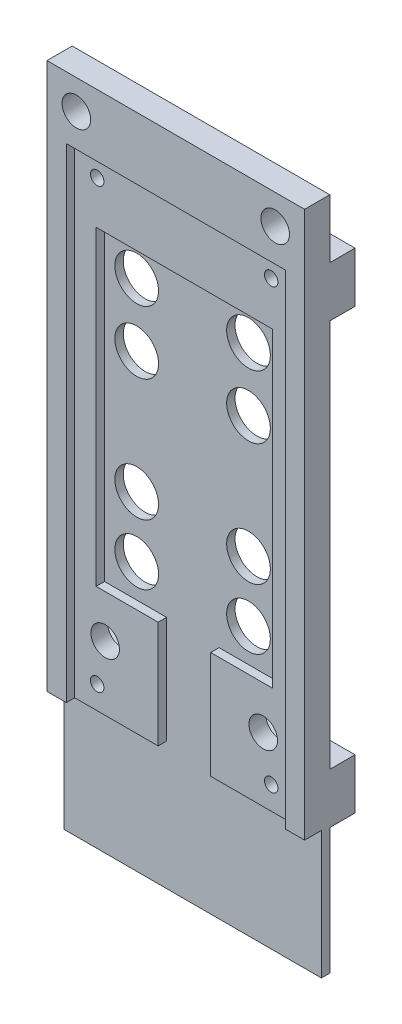
SolidWorks part; units mm, degrees
ref_plane "Front Plane" through (0, 0, 0) normal (0, 0, 1) x (1, 0, 0)
ref_plane "Top Plane" through (0, 0, 0) normal (0, 1, 0) x (1, 0, 0)
ref_plane "Right Plane" through (0, 0, 0) normal (1, 0, 0) x (0, 0, -1)
sketch "Sketch1" plane through (0, 0, 0) normal (0, 0, 1) x (1, 0, 0)
  line L0 (0, 0) -> (0, 81.2)
  line L1 (0, 81.2) -> (32.65, 81.2)
  line L2 (32.65, 81.2) -> (32.65, 0)
  line L3 (32.65, 0) -> (0, 0)
extrude "Boss-Extrude1" add sketch "Sketch1" along normal blind 1
sketch "Sketch2" plane through (0, 0, 1) normal (0, 0, 1) x (1, 0, 0)
  line L0 (0, 0) -> (0, 81.2)
  line L1 (0, 81.2) -> (32.65, 81.2)
  line L2 (32.65, 81.2) -> (32.65, 0)
  line L3 (32.65, 0) -> (31.65, 0)
  line L4 (0, 0) -> (32.65, 0) construction
  line L5 (31.65, 0) -> (31.65, 80.2)
  line L6 (0, 0) -> (1, 0)
  line L7 (1, 0) -> (1, 80.2)
  line L8 (1, 80.2) -> (31.65, 80.2)
extrude "Boss-Extrude2" add sketch "Sketch2" along normal blind 4
sketch "Sketch3" plane through (0, 0, 1) normal (0, 0, 1) x (1, 0, 0)
  line L0 (1, 80.2) -> (6.2, 80.2)
  line L1 (1, 80.2) -> (31.65, 80.2) construction
  line L2 (6.2, 80.2) -> (6.2, 75)
  line L3 (1, 80.2) -> (1, 75)
  line L4 (1, 0) -> (1, 80.2) construction
  line L5 (1, 75) -> (6.2, 75)
  line L6 (31.65, 80.2) -> (31.65, 75)
  line L7 (31.65, 80.2) -> (31.65, 0) construction
  line L8 (31.65, 75) -> (26.45, 75)
  line L9 (26.45, 75) -> (26.45, 80.2)
  line L10 (26.45, 80.2) -> (31.65, 80.2)
  line L11 (16.325, 0) -> (16.325, 15.2)
  line L12 (1, 0) -> (31.65, 0) construction
  line L13 (1, 15.2) -> (6.2, 15.2)
  line L14 (1, 15.2) -> (1, 20.4)
  line L15 (1, 20.4) -> (6.2, 20.4)
  line L16 (6.2, 20.4) -> (6.2, 15.2)
  line L17 (31.65, 15.2) -> (31.65, 20.4)
  line L18 (31.65, 15.2) -> (26.45, 15.2)
  line L19 (26.45, 15.2) -> (26.45, 20.4)
  line L20 (26.45, 20.4) -> (31.65, 20.4)
  line M18 (31.65, 0) -> (31.65, 80.2)
  line M19 (31.65, 80.2) -> (1, 80.2)
  line M20 (1, 80.2) -> (1, 0)
extrude "Boss-Extrude3" add sketch "Sketch3" along normal blind 1 contours L5 L2 M20 M19 | L16 L15 L13 M20 | L20 L19 L18 M18 | L10 L6 L8 L9
sketch3d "3DSketch1"
  line L0 (6.2, 80.2, 1) -> (26.45, 80.2, 1) construction
  circle A0 centre (11.325, 80.2, 4) radius 2
  circle A1 centre (21.325, 80.2, 4) radius 2
  point P17 (11.325, 82.2, 4)
  point P21 (21.325, 82.2, 4)
extrude "Cut-Extrude13" cut sketch "3DSketch1" along direction (0, 1, 0) on the side against the normal blind 15 contours A1 | A0
sketch3d "3DSketch2"
  line L0 (1, 0, 1) -> (31.65, 0, 1) construction
  line L1 (16.325, 80.2, 1) -> (16.325, 0, 1) construction
  line L2 (6.2, 80.2, 1) -> (26.45, 80.2, 1) construction
  circle A0 centre (9.675, 61.1, 1) radius 2.6
  circle A1 centre (22.975, 61.1, 1) radius 2.6
  circle A2 centre (9.675, 53.6, 1) radius 2.6
  circle A3 centre (22.975, 53.6, 1) radius 2.6
  circle A4 centre (9.675, 39.1, 1) radius 2.6
  circle A5 centre (22.975, 39.1, 1) radius 2.6
  circle A6 centre (9.675, 31.9, 1) radius 2.6
  circle A7 centre (22.975, 31.9, 1) radius 2.6
  point P13 (9.675, 61.1, 3.6)
  point P20 (22.975, 61.1, 3.6)
  point P25 (9.675, 53.6, 3.6)
  point P28 (22.975, 53.6, 3.6)
  point P31 (9.675, 39.1, 3.6)
  point P34 (22.975, 39.1, 3.6)
  point P37 (9.675, 31.9, 3.6)
  point P40 (22.975, 31.9, 3.6)
  dimension "D1" = 6.65
  dimension "D2" = 6.65
  dimension "D3" = 31.9
  dimension "D4" = 39.1
  dimension "D5" = 53.6
  dimension "D6" = 61.1
extrude "Cut-Extrude14" cut sketch "3DSketch2" along direction (0, 0, -1) on the side against the normal blind 24
sketch "Sketch7" plane through (0, 81.2, 0) normal (0, 1, 0) x (1, 0, 0)
  circle A0 centre (11.325, -4) radius 2
  circle A1 centre (21.3083, -4.003) radius 2
  arc M5 (9.5929, -5) -> (13.0571, -5) centre (11.325, -4) cw
  line M6 (13.0571, -5) -> (9.5929, -5)
extrude "Cut-Extrude20" cut sketch "Sketch7" against normal blind 6.9 contours A0 M6 | M5 M6 | A1
sketch "Sketch8" plane through (0, 0, 0) normal (0, -1, 0) x (1, 0, 0)
  line L0 (0, 5) -> (1, 5)
  line L1 (1, 5) -> (1, 0)
  line L2 (0, 0) -> (32.65, 0) construction
  line L3 (1, 0) -> (0, 0)
  line L4 (0, 0) -> (0, 5)
  line L5 (32.65, 0) -> (32.65, 5)
  line L6 (32.65, 5) -> (31.65, 5)
  line L7 (31.65, 5) -> (31.65, 0)
  line L8 (31.65, 0) -> (32.65, 0)
  line M9 (0, 0) -> (32.65, 0)
  line M14 (1, 1) -> (1, 5)
  line M15 (1, 5) -> (0, 5)
  line M16 (0, 5) -> (0, 0)
extrude "Cut-Extrude21" cut sketch "Sketch8" against normal through all contours L1 M14 M15 M16 M9 | L8 L5 L6 L7
sketch "Sketch9" plane through (31.65, 0, 0) normal (1, 0, 0) x (0, 0, -1)
  line L0 (-5, 80.2) -> (-5, 81.2)
  line L9 (-5, 80.2) -> (0, 80.2)
  line L10 (0, 81.2) -> (0, 0) construction
  line L11 (0, 80.2) -> (0, 81.2)
  line L12 (0, 81.2) -> (-5, 81.2)
extrude "Cut-Extrude23" cut sketch "Sketch9" against normal through all contours L11 L12 L0 L9
sketch "Sketch11" plane through (0, 0, 0) normal (0, 0, -1) x (-1, 0, 0)
  line L0 (-1, 80.2) -> (-11, 80.2)
  line L1 (-1, 80.2) -> (-31.65, 80.2) construction
  line L2 (-11, 80.2) -> (-11, 67.2)
  line L3 (-11, 67.2) -> (-1, 67.2)
  line L4 (-1, 80.2) -> (-1, 0) construction
  line L5 (-1, 67.2) -> (-1, 80.2)
  line L6 (-31.65, 80.2) -> (-31.65, 67.2)
  line L7 (-31.65, 80.2) -> (-31.65, 0) construction
  line L8 (-31.65, 80.2) -> (-21.65, 80.2)
  line L9 (-31.65, 67.2) -> (-21.65, 67.2)
  line L10 (-21.65, 67.2) -> (-21.65, 80.2)
  line L11 (-31.65, 73.2) -> (-21.65, 73.2)
  line L12 (-11, 73.2) -> (-1, 73.2)
  line L13 (-1, 21) -> (-1, 15)
  line L14 (-1, 15) -> (-11, 15)
  line L15 (-11, 15) -> (-11, 21)
  line L16 (-11, 21) -> (-1, 21)
  line L17 (-31.65, 21) -> (-21.65, 21)
  line L18 (-21.65, 21) -> (-21.65, 15)
  line L19 (-21.65, 15) -> (-31.65, 15)
  line L20 (-31.65, 15) -> (-31.65, 21)
  point P23 (-26.65, 70.2)
  point P26 (-26.65, 67.2)
  line M18 (-31.65, 80.2) -> (-31.65, 0)
  line M20 (-1, 0) -> (-1, 80.2)
  dimension "D1" = 21
  dimension "D2" = 10
  dimension "D3" = 13
  dimension "D4" = 10
  dimension "D5" = 13
  dimension "D6" = 7
extrude "Boss-Extrude4" add sketch "Sketch11" along normal blind 3 contours L19 L18 L17 M18 | L11 L6 L9 L10 | L12 L2 L3 M20 | L16 L13 L14 L15
sketch "Sketch12" plane through (0, 0, 2) normal (0, 0, 1) x (1, 0, 0)
  line L1 (31.65, 80.2) -> (31.65, 75) construction
  line L2 (1, 0) -> (31.65, 0) construction
  point P0 (26.675, 70.1)
  dimension "D1" = 70.1
  dimension "D2" = 4.975
hole_wizard "Tap Drill for M2x0.4 Tap1" positions "3DSketch3" profile "Sketch13" hole size "M2x0.4" standard "ANSI Metric" end condition through all
sketch3d "3DSketch3"
  point P0 (26.675, 70.1, 2)
sketch "Sketch13" plane through (26.675, 70.1, 2) normal (1, 0, 0) x (0, -1, 0)
  line L0 (0, 0) -> (0, 5)
  line L1 (0, 5) -> (0.8, 5)
  line L2 (0.8, 5) -> (0.8, 0)
  line L5 (0.8, 0) -> (0, 0)
  line L11 (0, -6.35) -> (0, 107.95) construction
  dimension "Thru Hole Dia." = 1.6
  dimension "Thru Hole Depth" = 5
sketch "Sketch14" plane through (0, 0, 2) normal (0, 0, 1) x (1, 0, 0)
  line L1 (1, 80.2) -> (1, 75) construction
  line L2 (1, 20.4) -> (1, 15.2) construction
  line L3 (1, 0) -> (31.65, 0) construction
  line L4 (31.65, 15.2) -> (31.65, 20.4) construction
  point P0 (5.975, 70.1)
  point P6 (5.975, 17.95)
  point P7 (26.6773, 17.95)
  point P14 (31.65, 17.8)
  dimension "D1" = 70.1
  dimension "D2" = 4.975
  dimension "D3" = 4.975
  dimension "D4" = 17.95
  dimension "D5" = 17.95
  dimension "D6" = 4.975
hole_wizard "Tap Drill for M2x0.4 Tap2" positions "3DSketch4" profile "Sketch15" hole size "M2x0.4" standard "ANSI Metric" end condition through all
sketch3d "3DSketch4"
  point P0 (5.975, 70.1, 2)
  point P3 (5.975, 17.95, 2)
  point P6 (26.6773, 17.95, 2)
sketch "Sketch15" plane through (5.975, 70.1, 2) normal (1, 0, 0) x (0, -1, 0)
  line L0 (0, 0) -> (0, 5)
  line L1 (0, 5) -> (0.8, 5)
  line L2 (0.8, 5) -> (0.8, 0)
  line L3 (49.7, 1) -> (-4.9, 1) construction
  line L5 (0.8, 0) -> (0, 0)
  line L11 (0, -6.35) -> (0, 107.95) construction
  dimension "Thru Hole Dia." = 1.6
  dimension "Thru Hole Depth" = 5
sketch "Sketch35" plane through (0, 0, 1) normal (0, 0, 1) x (1, 0, 0)
  circle A0 centre (5.975, 70.1) radius 0.8 construction
  point P0 (1, 0)
  point P1 (31.65, 0)
sketch "Sketch37" plane through (0, 0, 1) normal (0, 0, 1) x (1, 0, 0)
  line L0 (27.35, 65.45) -> (27.35, 27.45)
  line L1 (27.35, 27.45) -> (5.35, 27.45)
  line L2 (5.35, 27.45) -> (5.35, 65.45)
  line L3 (5.35, 65.45) -> (27.35, 65.45)
  line L4 (1, 0) -> (31.65, 0) construction
  line L5 (1, 20.4) -> (1, 75) construction
  line L6 (6.2, 80.2) -> (26.45, 80.2) construction
  line L7 (4.85, 65.45) -> (5.85, 65.45)
  line L8 (4.85, 65.45) -> (4.85, 27.45)
  line L9 (4.85, 27.45) -> (5.85, 27.45)
  line L10 (5.85, 65.45) -> (5.85, 27.45)
  line L11 (4.85, 65.45) -> (5.85, 27.45) construction
  line L12 (4.85, 27.45) -> (5.85, 65.45) construction
  line L13 (26.85, 65.45) -> (27.85, 65.45)
  line L14 (26.85, 65.45) -> (26.85, 27.45)
  line L15 (26.85, 27.45) -> (27.85, 27.45)
  line L16 (27.85, 65.45) -> (27.85, 27.45)
  line L17 (26.85, 65.45) -> (27.85, 27.45) construction
  line L18 (26.85, 27.45) -> (27.85, 65.45) construction
  line L19 (4.85, 65.95) -> (27.85, 65.95)
  line L20 (4.85, 65.95) -> (4.85, 64.95)
  line L21 (4.85, 64.95) -> (27.85, 64.95)
  line L22 (27.85, 65.95) -> (27.85, 64.95)
  line L23 (4.85, 65.95) -> (27.85, 64.95) construction
  line L24 (4.85, 64.95) -> (27.85, 65.95) construction
  line L25 (4.85, 27.95) -> (27.85, 27.95)
  line L26 (4.85, 27.95) -> (4.85, 26.95)
  line L27 (4.85, 26.95) -> (27.85, 26.95)
  line L28 (27.85, 27.95) -> (27.85, 26.95)
  line L29 (4.85, 27.95) -> (27.85, 26.95) construction
  line L30 (4.85, 26.95) -> (27.85, 27.95) construction
  line L31 (13.225, 27.95) -> (19.475, 27.95)
  line L32 (13.225, 27.95) -> (13.225, 26.95)
  line L33 (13.225, 26.95) -> (19.475, 26.95)
  line L34 (19.475, 27.95) -> (19.475, 26.95)
  line L35 (13.225, 27.95) -> (19.475, 26.95) construction
  line L36 (13.225, 26.95) -> (19.475, 27.95) construction
  line L37 (31.65, 75) -> (31.65, 20.4) construction
  line L38 (1, 20.4) -> (31.65, 20.4)
  line L39 (13.225, 26.95) -> (13.225, 20.4)
  line L40 (13.225, 20.4) -> (19.475, 20.4)
  line L41 (19.475, 20.4) -> (19.475, 26.95)
  line L42 (6.2, 15.2) -> (26.45, 15.2)
  line L43 (13.225, 20.4) -> (13.225, 15.2)
  line L44 (13.225, 15.2) -> (19.475, 15.2)
  line L45 (19.475, 15.2) -> (19.475, 20.4)
  point P6 (16.325, 0)
  point P7 (27.35, 46.45)
  point P8 (16.35, 65.45)
  point P11 (16.35, 67.1922)
  point P12 (28.5847, 46.45)
  point P13 (3.9097, 46.45)
  point P14 (7.0097, 46.45)
  point P15 (16.35, 28.6505)
  point P16 (16.35, 26.2431)
  point P17 (16.35, 64.0574)
  point P18 (25.7803, 46.45)
  point P19 (5.35, 46.45)
  point P24 (27.35, 46.45)
  point P29 (16.35, 65.45)
  point P34 (16.35, 27.45)
  point P39 (19.475, 27.45)
  point P40 (13.225, 27.45)
  point P41 (16.35, 27.45)
  point P46 (16.35, 46.45)
  line M17 (31.65, 75) -> (26.45, 75)
  line M18 (26.45, 75) -> (26.45, 80.2)
  line M19 (26.45, 80.2) -> (6.2, 80.2)
  line M20 (6.2, 80.2) -> (6.2, 75)
  line M21 (6.2, 75) -> (1, 75)
  line M22 (1, 75) -> (1, 20.4)
  line M23 (1, 20.4) -> (6.2, 20.4)
  line M24 (6.2, 20.4) -> (6.2, 18.7177)
  line M30 (26.45, 15.2) -> (26.45, 17.183)
  line M31 (26.45, 20.4) -> (31.65, 20.4)
  line M32 (31.65, 20.4) -> (31.65, 75)
  dimension "D1" = 46.45
  dimension "D2" = 15.35
  dimension "D3" = 1.7422
  dimension "D4" = 3.125
  dimension "D5" = 3.125
  dimension "D6" = 33.75
  dimension "D7" = 39
  dimension "D8" = 23
  dimension "D9" = 21
  dimension "D10" = 15.3
extrude "Boss-Extrude11" add sketch "Sketch37" along normal blind 1 contours L2 L25 L10 L21 | L8 L25 L2 L21 | L25 L8 L9 L2 | L25 L2 L1 L10 | L25 L0 L15 L16 | L25 L14 L1 L0 | L14 L25 L0 L21 | L0 L25 L16 L21 | L0 L21 L16 L13 | L14 L21 L0 L3 | L22 L19 L20 L7 L3 L13 | L10 L21 L14 L3 | L2 L21 L10 L3 | L8 L21 L2 L7 | L32 L1 L9 L26 L27 | L32 L25 L10 L1 | L1 L34 L27 L28 L15 | L25 L34 L1 L14 | L38 L16 L28 L27 L26 L8 L20 L19 L22 M23 M31 M32 M17 M18 M19 M20 M21 M22 | L43 L38 L42 M24 | L45 L42 L38 M30
sketch "Sketch40" plane through (0, 0, 2) normal (0, 0, 1) x (1, 0, 0)
  line L0 (31.65, 15.2) -> (31.65, 80.2) construction
  line L1 (1, 80.2) -> (1, 15.2) construction
  line L2 (29.35, 80.2) -> (29.35, 15.2)
  line L3 (31.65, 80.2) -> (1, 80.2) construction
  line L4 (31.65, 15.2) -> (19.475, 15.2) construction
  line L5 (3.3, 80.2) -> (3.3, 15.2)
  line L6 (1, 15.2) -> (13.225, 15.2) construction
  line L8 (29.35, 80.2) -> (31.65, 80.2)
  line L9 (29.35, 80.2) -> (29.35, 15.2)
  line L10 (29.35, 15.2) -> (31.65, 15.2)
  line L11 (31.65, 80.2) -> (31.65, 15.2)
  line L12 (3.3, 80.2) -> (1, 80.2)
  line L13 (3.3, 80.2) -> (3.3, 15.2)
  line L14 (3.3, 15.2) -> (1, 15.2)
  line L15 (1, 80.2) -> (1, 15.2)
  point P0 (29.35, 69.6505)
  point P4 (3.3, 67.3789)
  line M3 (31.65, 15.2) -> (31.65, 80.2)
  line M4 (31.65, 80.2) -> (1, 80.2)
  line M5 (1, 80.2) -> (1, 15.2)
  line M6 (1, 15.2) -> (13.225, 15.2)
  line M14 (19.475, 15.2) -> (31.65, 15.2)
  dimension "D1" = 2.3
  dimension "D2" = 2.3
extrude "Boss-Extrude12" add sketch "Sketch40" along normal blind 1 contours L2 M4 M14 M3 | L5 M4 M5 M6
sketch "Sketch41" plane through (0, 0, 2) normal (0, 0, 1) x (1, 0, 0)
  line L0 (3.3, 80.2) -> (3.3, 72.8)
  line L1 (3.3, 80.2) -> (3.3, 15.2) construction
  line L2 (3.3, 72.8) -> (29.35, 72.8)
  line L3 (29.35, 80.2) -> (29.35, 15.2) construction
  line L4 (29.35, 72.8) -> (29.35, 80.2)
  line L5 (29.35, 80.2) -> (3.3, 80.2)
extrude "Boss-Extrude13" add sketch "Sketch41" along normal blind 1
sketch "Sketch42" plane through (0, 0, 3) normal (0, 0, 1) x (1, 0, 0)
  line L0 (31.65, 80.2) -> (1, 80.2) construction
  line L1 (1, 80.2) -> (1, 15.2) construction
  line L2 (31.65, 15.2) -> (31.65, 80.2) construction
  point P0 (4.5, 76.7)
  point P5 (28.15, 76.7)
  dimension "D1" = 3.5
  dimension "D2" = 3.5
  dimension "D3" = 3.5
  dimension "D4" = 3.5
hole_wizard "M3 Clearance Hole1" positions "3DSketch5" profile "Sketch43" hole size "M3" standard "ANSI Metric" end condition through all
sketch3d "3DSketch5"
  line L0 (1, 0, 1) -> (31.65, 0, 1) construction
  point P0 (4.5, 76.7, 3)
  point P3 (28.15, 76.7, 3)
  dimension "D1" = 76.7261
  dimension "D2" = 76.7261
sketch "Sketch43" plane through (4.5, 76.7, 3) normal (1, 0, 0) x (0, -1, 0)
  line L0 (0, 0) -> (0, 6)
  line L1 (0, 6) -> (1.7, 6)
  line L2 (1.7, 6) -> (1.7, 0)
  line L5 (1.7, 0) -> (0, 0)
  line L11 (0, -6.35) -> (0, 107.95) construction
  dimension "Thru Hole Dia." = 3.4
  dimension "Thru Hole Depth" = 6
sketch "Sketch44" plane through (0, 0, 0) normal (0, 0, -1) x (-1, 0, 0)
  circle A0 centre (-28.15, 76.7) radius 3.18
sketch "Sketch45" plane through (0, 0, 2) normal (0, 0, 1) x (1, 0, 0)
  line L0 (3.3, 72.8) -> (29.35, 72.8)
sketch "Sketch47" plane through (0, 0, 2) normal (0, 0, 1) x (1, 0, 0)
  line L0 (1, 80.2) -> (1, 15.2) construction
  line L1 (1, 0) -> (31.65, 0) construction
  line L2 (31.65, 15.2) -> (31.65, 0) construction
  point P0 (6.925, 22.85)
  point P5 (25.725, 22.85)
  dimension "D1" = 5.925
  dimension "D2" = 22.85
  dimension "D3" = 5.925
hole_wizard "M3 Clearance Hole2" positions "3DSketch6" profile "Sketch48" hole size "M3" standard "ANSI Metric" end condition through all
sketch3d "3DSketch6"
  point P0 (6.925, 22.85, 2)
  point P3 (25.725, 22.85, 2)
sketch "Sketch48" plane through (6.925, 22.85, 2) normal (1, 0, 0) x (0, -1, 0)
  line L0 (0, 0) -> (0, 5)
  line L1 (0, 5) -> (1.7, 5)
  line L2 (1.7, 5) -> (1.7, 0)
  line L5 (1.7, 0) -> (0, 0)
  line L11 (0, -6.35) -> (0, 107.95) construction
  dimension "Thru Hole Dia." = 3.4
  dimension "Thru Hole Depth" = 5
